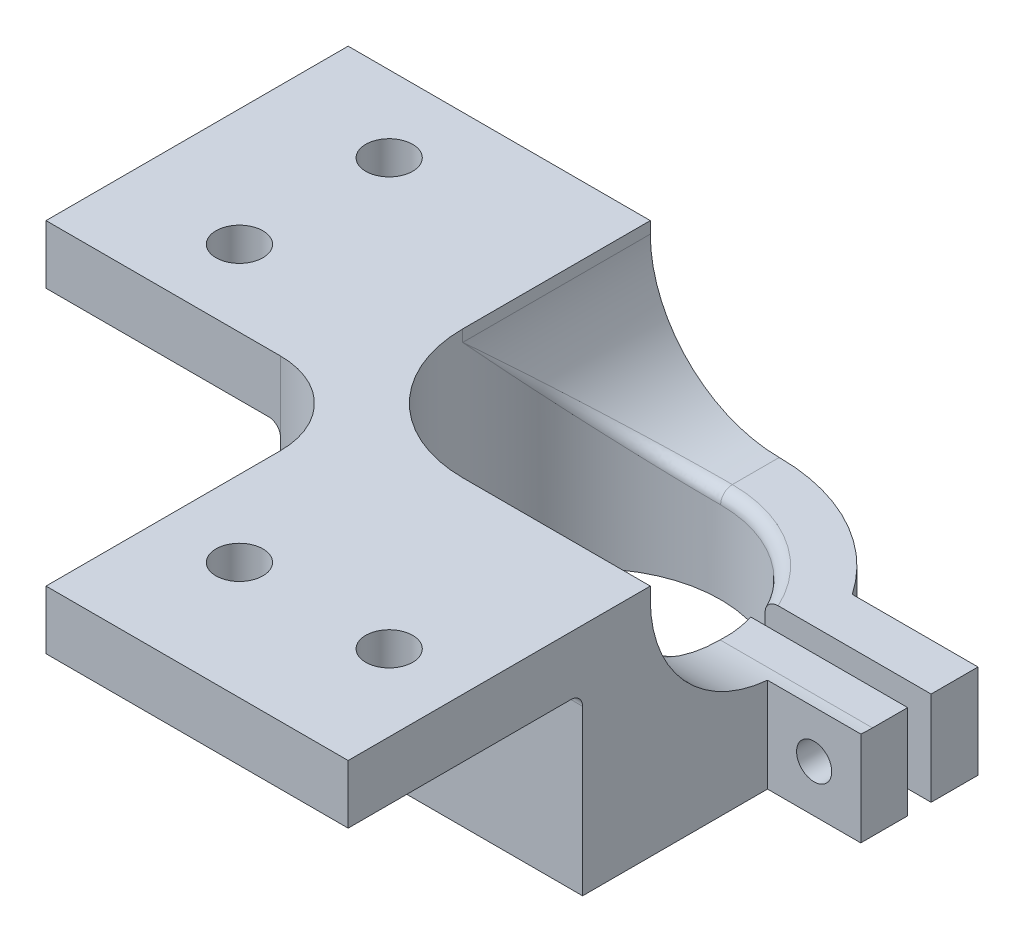
SolidWorks part; units mm, degrees
ref_plane "Front Plane" through (0, 0, 0) normal (0, 0, 1) x (1, 0, 0)
ref_plane "Top Plane" through (0, 0, 0) normal (0, 1, 0) x (1, 0, 0)
ref_plane "Right Plane" through (0, 0, 0) normal (1, 0, 0) x (0, 0, -1)
sketch "Sketch1" plane through (0, 0, 0) normal (0, 1, 0) x (1, 0, 0)
  line L0 (36.775, 52.775) -> (0, 52.775)
  line L1 (20, 0) -> (0, 0) construction
  line L4 (0, 0) -> (0, 20) construction
  line L5 (52.775, 36.775) -> (52.775, 20)
  line L6 (52.775, 20) -> (52.775, 0)
  line L7 (20, 60) -> (0, 60) construction
  line L8 (20, 60) -> (20, 20) construction
  line L10 (0, 60) -> (0, 20) construction
  line L11 (52.775, 0) -> (27, 0)
  line L12 (27, 0) -> (27, 20)
  line L13 (60, 0) -> (20, 0) construction
  line L14 (60, 0) -> (60, 20) construction
  line L15 (60, 20) -> (20, 20) construction
  line L17 (20, 27) -> (0, 27)
  line L18 (0, 27) -> (0, 52.775)
  line L19 (10, 60) -> (10, 27) construction
  line L20 (0, 52.775) -> (10, 46.275) construction
  line L21 (0, 0) -> (20, 20) construction
  line L23 (10, 33.5) -> (0, 27) construction
  circle A0 centre (36.775, 36.775) radius 4 construction
  circle A1 centre (36.775, 36.775) radius 11
  circle A2 centre (36.775, 36.775) radius 16 construction
  arc A3 (20, 27) -> (27, 20) centre (20, 20) cw
  arc A4 (36.775, 52.775) -> (52.775, 36.775) centre (36.775, 36.775) cw
  circle A5 centre (10, 46.275) radius 2
  circle A6 centre (10, 33.5) radius 2
  circle A7 centre (46.275, 10) radius 2
  circle A8 centre (33.5, 10) radius 2
  point P0 (0, 0)
  dimension "D5" = 16.775
  dimension "D6" = 16.775
  dimension "D7" = 8
  dimension "D8" = 22
  dimension "D10" = 7
  dimension "D11" = 4
  dimension "D12" = 6.5
  dimension "D1" = 20
  dimension "D2" = 20
  dimension "D3" = 40
  dimension "D4" = 40
  dimension "D9" = 5
extrude "Boss-Extrude1" add sketch "Sketch1" against normal blind 5 contours A4 L0 L18 L17 A3 L12 L11 L6 L5 A7 A6 A5 A1 A8
sketch "Sketch6" plane through (0, -5, 0) normal (0, -1, 0) x (1, 0, 0)
  line L0 (20, -27) -> (20, -52.775)
  line L1 (36.775, -52.775) -> (0, -52.775) construction
  line L3 (27, -20) -> (52.775, -20)
  line L4 (52.775, -36.775) -> (52.775, 0) construction
  line L6 (52.775, -20) -> (52.775, -36.775)
  line L7 (20, -52.775) -> (36.775, -52.775)
  arc A0 (36.775, -52.775) -> (52.775, -36.775) centre (36.775, -36.775) ccw construction
  arc A1 (36.775, -52.775) -> (52.775, -36.775) centre (36.775, -36.775) ccw
  arc A2 (20, -27) -> (27, -20) centre (20, -20) ccw construction
  arc A3 (20, -27) -> (27, -20) centre (20, -20) ccw
extrude "Boss-Extrude2" add sketch "Sketch6" along normal blind 15
sketch "Sketch7" plane through (0, -5, 0) normal (0, 1, 0) x (1, 0, 0)
  circle A0 centre (36.775, 36.775) radius 11 construction
  circle A1 centre (36.775, 36.775) radius 11
extrude "Cut-Extrude1" cut sketch "Sketch7" against normal through all both and the other way through all
fillet "Fillet1" radius 1 2 edges at (39.8875, -5, -20) (20, -5, -39.8875)
sketch "Sketch8" plane through (0, 0, 0) normal (0, 1, 0) x (1, 0, 0)
  line L0 (25.775, 52.775) -> (25.775, 36.775)
  line L1 (36.775, 52.775) -> (0, 52.775) construction
  line L3 (36.775, 25.775) -> (52.775, 25.775)
  line L4 (52.775, 36.775) -> (52.775, 0) construction
  circle A0 centre (36.775, 36.775) radius 11 construction
  arc A1 (25.775, 52.775) -> (52.775, 25.775) centre (36.775, 36.775) cw
  arc A2 (25.775, 36.775) -> (36.775, 25.775) centre (36.775, 36.775) ccw
extrude "Cut-Extrude2" cut sketch "Sketch8" against normal blind 12
sketch "Sketch9" plane through (0, -12, 0) normal (0, 1, 0) x (1, 0, 0)
  line L0 (52.775, 36.775) -> (52.775, 25.775) construction
  line L1 (41.2689, 39.775) -> (52.775, 39.775)
  line L2 (41.2689, 39.775) -> (41.2689, 41.775)
  line L3 (41.2689, 41.775) -> (52.775, 41.775)
  line L4 (52.775, 39.775) -> (52.775, 41.775)
  line L5 (41.2689, 39.775) -> (52.775, 41.775) construction
  line L6 (41.2689, 41.775) -> (52.775, 39.775) construction
  line L7 (36.775, 25.775) -> (52.775, 25.775) construction
  arc A0 (36.775, 25.775) -> (25.775, 36.775) centre (36.775, 36.775) ccw construction
  point P0 (47.022, 40.775)
  dimension "D1" = 2
  dimension "D2" = 14
extrude "Cut-Extrude4" cut sketch "Sketch9" against normal through all both and the other way through all
sketch "Sketch10" plane through (0, -12, 0) normal (0, 1, 0) x (1, 0, 0)
  line L0 (52.4912, 39.775) -> (47.358, 39.775) construction
  line L1 (46.573, 41.775) -> (60.7295, 41.775)
  line L2 (46.573, 41.775) -> (46.573, 45.775)
  line L3 (46.573, 45.775) -> (60.7295, 45.775)
  line L4 (60.7295, 41.775) -> (60.7295, 45.775)
  line L5 (47.7295, 35.775) -> (60.7295, 35.775)
  line L6 (47.7295, 35.775) -> (47.7295, 39.775)
  line L7 (47.7295, 39.775) -> (60.7295, 39.775)
  line L8 (60.7295, 35.775) -> (60.7295, 39.775)
  arc A0 (36.775, 25.775) -> (47.358, 39.775) centre (36.775, 36.775) ccw construction
  dimension "D1" = 4
  dimension "D2" = 4
  dimension "D3" = 13
extrude "Boss-Extrude3" add sketch "Sketch10" against normal up to surface (8 mm away) up to face at (39.0593, -20, -36.8324)
fillet "Fillet2" radius 11 2 edges at (25.775, -12, -44.775) (44.775, -12, -25.775)
fillet "Fillet4" radius 1 3 edges at (42.5196, -12, -46.1558) (28.9968, -8.7782, -44.5532) (44.1912, -8.4162, -28.651)
sketch "Sketch11" plane through (0, 0, -35.775) normal (0, 0, 1) x (1, 0, 0)
  line L0 (60.7295, -11.9545) -> (52.775, -20) construction
  line L1 (52.775, -20) -> (52.775, -11.9545) construction
  line L2 (52.775, -11.9545) -> (60.7295, -20) construction
  circle A0 centre (56.7522, -15.9772) radius 1.5
  point P4 (56.7522, -15.9772)
  dimension "D1" = 3
extrude "Cut-Extrude5" cut sketch "Sketch11" against normal through all
